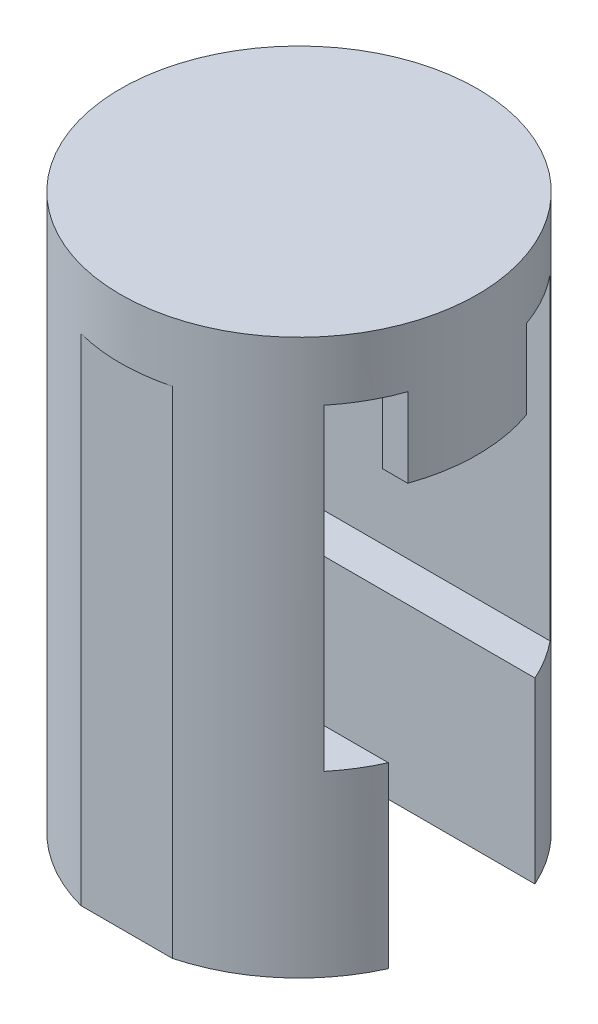
SolidWorks part; units mm, degrees
ref_plane "Front Plane" through (0, 0, 0) normal (0, 0, 1) x (1, 0, 0)
ref_plane "Top Plane" through (0, 0, 0) normal (0, 1, 0) x (1, 0, 0)
ref_plane "Right Plane" through (0, 0, 0) normal (1, 0, 0) x (0, 0, -1)
sketch "Sketch1" plane through (0, 0, 0) normal (0, 1, 0) x (1, 0, 0)
  circle A0 centre (0, 0) radius 4.5
  dimension "D1" = 9
extrude "Boss-Extrude1" add sketch "Sketch1" along normal blind 1.5
sketch "Sketch2" plane through (0, 0, 0) normal (0, -1, 0) x (1, 0, 0)
  line L0 (-3.4825, 2.85) -> (3.4825, 2.85)
  line L1 (3.4825, -2.85) -> (-3.4825, -2.85)
  line L2 (-1.1522, 4.35) -> (1.1522, 4.35)
  line L3 (-1.1522, -4.35) -> (1.1522, -4.35)
  line L4 (3.6, 1.5) -> (4.2426, 1.5)
  line L5 (3.6, -1.5) -> (4.2426, -1.5)
  line L6 (-3.6, 1.5) -> (-4.2426, 1.5)
  line L7 (-3.6, -1.5) -> (-4.2426, -1.5)
  circle A0 centre (0, 0) radius 4.5 construction
  circle A3 centre (0, 0) radius 4.5
  arc A4 (-2.6622, 2.85) -> (-2.6622, -2.85) centre (0, 0) ccw
  arc A5 (2.6622, -2.85) -> (2.6622, 2.85) centre (0, 0) ccw
  circle M9 centre (0, 0) radius 4.5
  dimension "D4" = 7.8
  dimension "D1" = 5.7
  dimension "D2" = 1.5
  dimension "D3" = 1.5
  dimension "D5" = 3
  dimension "D6" = 3
extrude "Boss-Extrude2" add sketch "Sketch2" along normal blind 2 contours L0 A4 | L1 A4 | A4 L5 L4 M9 | A4 L6 L7 M9 region at (0, 0, 3.4952) region at (-4.1067, 0, 0) region at (4.1067, 0, 0) region at (0, 0, -3.4952)
sketch "Sketch3" plane through (0, -2, 0) normal (0, -1, 0) x (1, 0, 0)
  line L0 (-3.4825, 2.85) -> (3.4825, 2.85)
  line L1 (-1.1522, 4.35) -> (1.1522, 4.35)
  line L2 (-3.2404, -2.85) -> (3.4825, -2.85)
  line L3 (3.4825, -2.85) -> (-3.4825, -2.85) construction
  line L4 (-1.1522, -4.35) -> (1.1522, -4.35)
  circle A0 centre (0, 0) radius 4.5
  arc M1 (-3.4825, -2.85) -> (-1.1522, -4.35) centre (0, 0) ccw
  line M2 (-1.1522, -4.35) -> (1.1522, -4.35)
  arc M3 (1.1522, -4.35) -> (3.4825, -2.85) centre (0, 0) ccw
  line M4 (3.4825, -2.85) -> (-3.4825, -2.85)
extrude "Boss-Extrude3" add sketch "Sketch3" along normal blind 6 contours L0 A0 L1 | M4 M1 M2 M3 region at (0, -2, 3.4952) region at (0, -2, -3.4952)
sketch "Sketch4" plane through (0, -8, 0) normal (0, -1, 0) x (1, 0, 0)
  line L0 (-1.1522, -4.35) -> (1.1522, -4.35)
  line L1 (1.1522, 4.35) -> (-1.1522, 4.35)
  line L2 (-4.1021, 1.85) -> (4.1021, 1.85)
  line L3 (4.1021, -1.85) -> (-4.1021, -1.85)
  line L4 (3.4825, -2.85) -> (-3.4825, -2.85) construction
  line L6 (-3.4825, 2.85) -> (3.4825, 2.85) construction
  circle A0 centre (0, 0) radius 4.5
  arc A1 (-1.1522, 4.35) -> (-3.4825, 2.85) centre (0, 0) ccw construction
  point P14 (-3.5095, 1.9993)
  point P18 (-2.4357, 3.7839)
  line M3 (3.4825, -2.85) -> (-3.4825, -2.85)
  arc M4 (-3.4825, -2.85) -> (-1.1522, -4.35) centre (0, 0) ccw
  line M5 (-1.1522, -4.35) -> (1.1522, -4.35)
  arc M6 (1.1522, -4.35) -> (3.4825, -2.85) centre (0, 0) ccw
  dimension "D1" = 1
  dimension "D2" = 1
extrude "Boss-Extrude4" add sketch "Sketch4" along normal blind 4.5 contours M6 M3 M4 M5 | A0 L3 M3 | L2 A0 L1 region at (0, -8, -3.4952) region at (0, -8, -2.3366) region at (0, -8, 2.9203)
